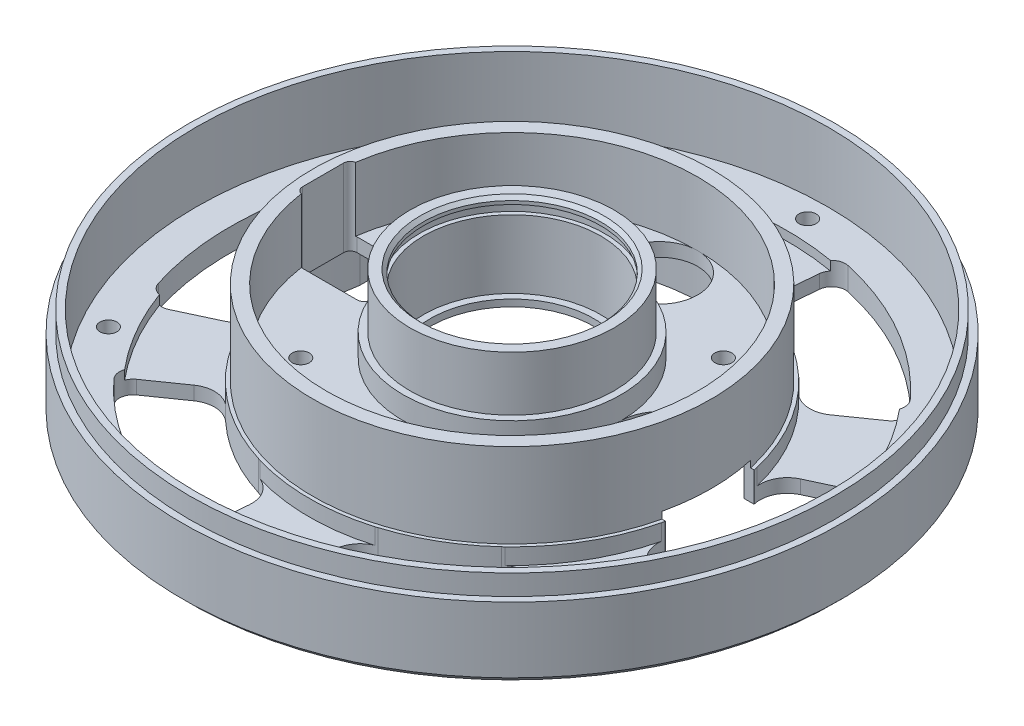
SolidWorks part; units mm, degrees
material "5052-H32"
ref_plane "Front Plane" through (0, 0, 0) normal (0, 0, 1) x (1, 0, 0)
ref_plane "Top Plane" through (0, 0, 0) normal (0, 1, 0) x (1, 0, 0)
ref_plane "Right Plane" through (0, 0, 0) normal (1, 0, 0) x (0, 0, -1)
ref_axis "Axis1" through (0, 0, 0) along (0, 1, 0)
sketch "Sketch1" plane through (0, 0, 0) normal (0, 0, 1) x (1, 0, 0)
  line L0 (0, 0) -> (0, -50000) construction
  line L1 (-13, 8.15) -> (-13, -4.15)
  line L2 (-13, -4.15) -> (-12, -4.15)
  line L4 (45.1, 8.15) -> (-45.1, 8.15) construction
  line L5 (-12.75, -4.15) -> (12.75, -4.15) construction
  line L7 (-13, 8.15) -> (-14.98, 8.15)
  line L8 (-14.98, 8.15) -> (-14.98, -3.15)
  line L9 (-14.98, -3.15) -> (-28.25, -3.15)
  line L10 (-12, -5.15) -> (-28.25, -5.15)
  line L12 (-28.25, -5.15) -> (-28.25, -3.15)
  line L13 (-29.25, 6) -> (-29.25, -6) construction
  line L16 (-12, -4.15) -> (-12, -5.15)
  dimension "D1" = 1
  dimension "D2" = 29.96
  dimension "D3" = 2
  dimension "D4" = 1
  dimension "D5" = 1
  dimension "D6" = 26
revolve "Revolve1" add sketch "Sketch1" angle 360 about L0
sketch "Sketch4" plane through (0, 0, 0) normal (0, 0, 1) x (1, 0, 0)
  line L1 (-29.75, -8.5) -> (-40.35, -8.5)
  line L2 (-46.35, -7.15) -> (-46.35, 3)
  line L3 (-46.35, 3) -> (-47.35, 3)
  line L4 (-47.35, 3) -> (-47.35, 0)
  line L5 (-47.35, 0) -> (-48.35, 0)
  line L6 (-48.35, 0) -> (-48.35, -9.6235)
  line L7 (-47.4735, -10.5) -> (-28.25, -10.5)
  line L8 (-28.25, -10.5) -> (-26.25, -5.15) construction
  line L9 (-29.75, -8.5) -> (-29.75, -6.1361)
  line L10 (-26.25, -5.15) -> (-26.25, -3.15)
  line L12 (-48.35, -9.6235) -> (-47.4735, -10.5)
  line L13 (-45.1, 8.15) -> (-45.1, -6.15) construction
  line L14 (-46.35, -7.15) -> (-40.35, -7.15)
  line L15 (-40.35, -7.15) -> (-40.35, -8.5)
  line L16 (-45.1, -6.15) -> (45.1, -6.15) construction
  line L18 (-44.85, -7.15) -> (-44.85, -10.5) construction
  line L20 (-41.85, -7.15) -> (-41.85, -10.5) construction
  line L21 (-26.25, -5.15) -> (-28.25, -5.15)
  line L22 (-29.75, -6.1361) -> (-29.23, -6.1361)
  line L23 (-28.25, -5.15) -> (-28.25, -10.5)
  line L24 (-29.23, -6.1361) -> (-29.23, -3.15)
  line L25 (-29.23, -3.15) -> (-26.25, -3.15)
  line L26 (28.25, -3.15) -> (-28.25, -3.15) construction
  line L27 (-39.5, -7.5) -> (39.5, -7.5) construction
  line L28 (0, 0) -> (0, 50000) construction
  line L29 (-30.25, -6) -> (-30.25, -7.5) construction
  line L33 (-28.25, -5.15) -> (28.25, -5.15) construction
  dimension "D1" = 2
  dimension "D2" = 3
  dimension "D3" = 1
  dimension "D4" = 2
  dimension "D5" = 0.5
  dimension "D6" = 1
  dimension "D7" = 1.25
  dimension "D8" = 135
  dimension "D9" = 3
  dimension "D10" = 1.5
  dimension "D11" = 1.5
  dimension "D12" = 2
  dimension "D13" = 1.5
  dimension "D14" = 58.46
revolve "Revolve2" add sketch "Sketch4" angle 360 about axis through (0, 0, 0) along (0, 1, 0)
sketch "Sketch6" plane through (0, 0, 0) normal (0, 0, 1) x (1, 0, 0)
  line L0 (-29.23, 6.233) -> (-27.23, 6.233)
  line L1 (-27.23, 6.233) -> (-27.23, -3.15)
  line L2 (-27.23, -3.15) -> (-29.23, -3.15)
  line L3 (-29.23, -3.15) -> (-29.23, 6.233)
  line L6 (29.23, -3.15) -> (-29.23, -3.15) construction
  dimension "D1" = 2
revolve "Revolve3" add sketch "Sketch6" angle 360 about axis through (0, 0, 0) along (0, 1, 0)
sketch "Sketch7" plane through (0, 0, 0) normal (0, 0, 1) x (1, 0, 0)
  line L0 (40.35, -8.5) -> (-40.35, -8.5) construction
  line L1 (-29.7176, -6.1376) -> (-29.23, -6.1376)
  line L2 (-29.73, -6.15) -> (-29.73, -8.5)
  line L3 (-29.73, -8.5) -> (-29.23, -8.5)
  line L4 (-29.23, -6.1376) -> (-29.23, -8.5)
  line L5 (-29.23, 6.233) -> (-29.23, -6.1361) construction
  line L6 (-29.7176, -6.1376) -> (-29.73, -6.15)
  line L7 (29.75, -8.5) -> (-29.75, -8.5) construction
  line L8 (-31.759, -6.15) -> (-25.7399, -6.15) construction
  dimension "D1" = 135
  dimension "D2" = 0.5
revolve "Revolve4" add sketch "Sketch7" angle 360 about axis through (0, 0, 0) along (0, 1, 0)
sketch "Sketch8" plane through (0, -5.15, 0) normal (0, -1, 0) x (1, 0, 0)
  circle A0 centre (-15.5, 15.5) radius 3.5
  circle A1 centre (15.5, 15.5) radius 3.5
  circle A2 centre (15.5, -15.5) radius 3.5
  circle A3 centre (-15.5, -15.5) radius 3.5
  dimension "D1" = 7
sketch "Sketch10" plane through (0, 0, 0) normal (0, 0, 1) x (1, 0, 0)
  line L0 (-15.25, 0.15) -> (15.25, 0.15) construction
  line L1 (-14.98, -3.15) -> (-15.98, -3.15)
  line L2 (-14.98, -3.15) -> (-14.98, 0.15)
  line L3 (-14.98, 0.15) -> (-15.98, 0.15)
  line L4 (-15.98, -3.15) -> (-15.98, 0.15)
  line L5 (-14.98, 8.15) -> (-14.98, -3.15) construction
  line L6 (14.98, -3.15) -> (-14.98, -3.15) construction
  dimension "D1" = 1
revolve "Revolve5" add sketch "Sketch10" angle 360 about axis through (0, 0, 0) along (0, 1, 0)
sketch "Sketch12" plane through (0, 0, 0) normal (0, 1, 0) x (1, 0, 0)
  circle A0 centre (21.605, 0) radius 5.625
  circle A1 centre (0, 0) radius 15.98 construction
  circle A2 centre (0, 0) radius 27.23 construction
extrude "Cut-Extrude2" cut sketch "Sketch12" against normal through all
pattern_circular "CirPattern3" count 4 over 360 about axis through (0, 0, 0) along (0, 1, 0) skipping 2, 3 of "Cut-Extrude2"
extrude "Boss-Extrude1" add sketch "Sketch8" along normal up to surface (3.85 mm away)
hole_wizard "M3x0.5 Tapped Hole1" positions "Sketch14" profile "Sketch15" tap size "M3x0.5" standard "ANSI Metric" end condition through all
sketch "Sketch14" plane through (0, -9, 0) normal (0, -1, 0) x (-1, 0, 0)
  point P0 (-15.5, 15.5)
  point P3 (15.5, 15.5)
  point P6 (15.5, -15.5)
  point P9 (-15.5, -15.5)
cosmetic thread "Hole Thread1" parameters "D2"=3
cosmetic thread "Hole Thread2" parameters "D2"=3
cosmetic thread "Hole Thread3" parameters "D2"=3
cosmetic thread "Hole Thread4" parameters "D2"=3
sketch "Sketch15" plane through (15.5, -9, -15.5) normal (1, 0, 0) x (0, 0, -1)
  line L0 (0, 0) -> (0, 17.15)
  line L1 (0, 17.15) -> (1.25, 17.15)
  line L2 (1.25, 17.15) -> (1.25, 0)
  line L5 (1.25, 0) -> (0, 0)
  line L11 (0, -6.35) -> (0, 107.95) construction
  dimension "Thru Tap Drill Dia." = 2.5
  dimension "Thru Tap Drill Depth" = 17.15
hole_wizard "M3x0.5 Tapped Hole3" positions "Sketch19" profile "Sketch20" tap size "M3x0.5" standard "ANSI Metric" end condition through all
sketch "Sketch19" plane through (0, -10.5, 0) normal (0, -1, 0) x (-1, 0, 0)
  line L0 (0, 0) -> (0, 43.35) construction
  line L3 (0, 0) -> (-50000, 0) construction
  circle A1 centre (0, 0) radius 43.35 construction
  circle A2 centre (0, 0) radius 40.35 construction
  point P0 (0, 43.35)
  dimension "D1" = 3
  dimension "D2" = 90
sketch "Sketch20" plane through (0, -10.5, -43.35) normal (1, 0, 0) x (0, 0, -1)
  line L0 (0, 0) -> (0, 18.65)
  line L1 (0, 18.65) -> (1.25, 18.65)
  line L2 (1.25, 18.65) -> (1.25, 0.5)
  line L3 (1.25, 0.5) -> (1.75, 0)
  line L5 (1.75, 0) -> (0, 0)
  line L6 (-1.25, 0.5) -> (-1.75, 0) construction
  line L11 (0, -6.35) -> (0, 107.95) construction
  dimension "Thru Tap Drill Dia." = 2.5
  dimension "Thru Tap Drill Depth" = 18.65
  dimension "Near C'Sink Dia." = 3.5
  dimension "Near C'Sink Angle" = 90
cosmetic thread "Hole Thread7" parameters "D2"=3
pattern_circular "CirPattern4" count 6 over 360 about axis through (0, 0, 0) along (0, 1, 0) of "M3x0.5 Tapped Hole3"
sketch "Sketch24" plane through (0, -10.5, 0) normal (0, -1, 0) x (1, 0, 0)
  line L9 (-25.6489, 5.5) -> (-44.2117, 5.5)
  line L10 (-25.6489, 5.5) -> (-25.6489, -5.5)
  line L11 (-25.6489, -5.5) -> (-44.2117, -5.5)
  line L12 (-46.2117, 3.5) -> (-46.2117, -3.5)
  arc A5 (-44.2117, -5.5) -> (-46.2117, -3.5) centre (-44.2117, -3.5) cw
  arc A6 (-44.2117, 5.5) -> (-46.2117, 3.5) centre (-44.2117, 3.5) ccw
  circle A7 centre (0, 0) radius 46.35 construction
  point P5 (-25.6489, 0)
  dimension "D2" = 2
  dimension "D1" = 11
extrude "Cut-Extrude6" [suppressed] cut sketch "Sketch24" against normal up to surface (1.5 mm away)
sketch "Sketch25" plane through (0, -10.5, 0) normal (0, -1, 0) x (1, 0, 0)
  line L5 (-25.6489, 5.5) -> (-44.2117, 5.5) construction
  line L9 (-34.6807, 5.5) -> (-44.2117, 5.5)
  line L10 (-34.6807, 5.5) -> (-34.6807, -5.5)
  line L11 (-34.6807, -5.5) -> (-44.2117, -5.5)
  line L12 (-46.2117, 3.5) -> (-46.2117, -3.5)
  line L13 (-25.6489, -5.5) -> (-44.2117, -5.5) construction
  line L14 (-46.2117, 3.5) -> (-46.2117, -3.5) construction
  arc A3 (-44.2117, -5.5) -> (-46.2117, -3.5) centre (-44.2117, -3.5) cw
  arc A4 (-44.2117, 5.5) -> (-46.2117, 3.5) centre (-44.2117, 3.5) ccw
  point P12 (-46.2117, -5.5)
  dimension "D1" = 2
extrude "Cut-Extrude7" [suppressed] cut sketch "Sketch25" against normal through all
sketch "Sketch26" plane through (0, 0, 0) normal (0, 1, 0) x (1, 0, 0)
  line L0 (0, 0) -> (-50000, 0) construction
  line L1 (31.1951, 11.1252) -> (36.6728, 13.6795)
  line L2 (31.1951, -11.1252) -> (36.6728, -13.6795)
  arc A0 (39.4249, 12.47) -> (39.4249, -12.47) centre (0, 0) cw
  arc A1 (28.9857, 6.6106) -> (28.9857, -6.6106) centre (0, 0) cw
  arc A2 (28.9857, -6.6106) -> (31.1951, -11.1252) centre (32.8856, -7.5) ccw
  arc A3 (28.9857, 6.6106) -> (31.1951, 11.1252) centre (32.8856, 7.5) cw
  circle A4 centre (0, 0) radius 46.35 construction
  arc A6 (39.4249, -12.47) -> (36.6728, -13.6795) centre (37.518, -11.8669) cw
  arc A7 (39.4249, 12.47) -> (36.6728, 13.6795) centre (37.518, 11.8669) ccw
  circle A8 centre (0, 0) radius 29.23 construction
  point P12 (28.108, -9.6857)
  point P15 (28.108, 9.6857)
  point P20 (38.6807, -14.6158)
  point P26 (38.6807, 14.6158)
  dimension "D1" = 4
  dimension "D2" = 0.5
  dimension "D4" = 2
  dimension "D6" = 5
  dimension "D3" = 50
  dimension "D5" = 15
extrude "Cut-Extrude8" cut sketch "Sketch26" against normal through all both and the other way through all
pattern_circular "CirPattern5" count 6 over 360 about axis through (0, 0, 0) along (0, 1, 0) of "Cut-Extrude8"
sketch "Sketch30" plane through (0, -10.5, 0) normal (0, -1, 0) x (1, 0, 0)
  line L1 (6.6135, 5) -> (34.3769, 5)
  line L2 (6.6135, 5) -> (6.6135, -5)
  line L3 (6.6135, -5) -> (34.3769, -5)
  line L4 (34.3769, 5) -> (34.3769, -5)
  point P4 (6.6135, 0)
  dimension "D1" = 10
extrude "Cut-Extrude13" [suppressed] cut sketch "Sketch30" against normal up to surface (5.35 mm away) up to face at (-15.5, -5.15, -19)
sketch "Sketch31" plane through (0, 0, 0) normal (0, 0, 1) x (1, 0, 0)
  line L0 (0, 0) -> (0, -50000) construction
  line L1 (13, 8.15) -> (-13, 8.15) construction
  line L2 (-5.4339, 7.15) -> (-13.6, 7.15)
  line L3 (-5.4339, 7.15) -> (-5.4339, 5.85)
  line L4 (-5.4339, 5.85) -> (-13.6, 5.85)
  line L5 (-13.6, 7.15) -> (-13.6, 5.85)
  dimension "D1" = 1.3
  dimension "D2" = 1
  dimension "D3" = 27.2
revolve "Cut-Revolve1" cut sketch "Sketch31" angle 360 about L0
chamfer "Chamfer1" distance 0.5 angle 45 1 edges at (0, 8.15, 13)
sketch "Sketch32" plane through (0, 0, 0) normal (0, 1, 0) x (1, 0, 0)
  line L1 (-18.73, 4) -> (-26.73, 4)
  line L2 (-17.73, 3) -> (-17.73, -3)
  line L3 (-18.73, -4) -> (-26.73, -4)
  line L4 (-27.73, 3) -> (-27.73, -3)
  arc A0 (-26.73, 4) -> (-27.73, 3) centre (-26.73, 3) ccw
  arc A1 (-17.73, -3) -> (-18.73, -4) centre (-18.73, -3) cw
  arc A2 (-26.73, -4) -> (-27.73, -3) centre (-26.73, -3) cw
  arc A3 (-18.73, 4) -> (-17.73, 3) centre (-18.73, 3) cw
  circle A4 centre (0, 0) radius 27.23 construction
  circle A5 centre (0, 0) radius 27.23 construction
  point P4 (-17.73, 0)
  point P16 (-27.23, 0)
  dimension "D2" = 1
  dimension "D3" = 0.5
  dimension "D1" = 8
  dimension "D4" = 10
extrude "Cut-Extrude14" cut sketch "Sketch32" against normal through all both and the other way through all
sketch "Sketch33" plane through (0, 0, 0) normal (0, 1, 0) x (1, 0, 0)
  line L1 (33.3439, -6.5) -> (25.7584, -6.5)
  line L2 (33.3439, -6.5) -> (33.3439, 6.5)
  line L3 (33.3439, 6.5) -> (25.7584, 6.5)
  line L4 (25.7584, -6.5) -> (25.7584, 6.5)
  line L5 (33.3439, -6.5) -> (25.7584, 6.5) construction
  line L6 (33.3439, 6.5) -> (25.7584, -6.5) construction
  point P0 (29.5512, 0)
  dimension "D1" = 13
extrude "Cut-Extrude15" cut sketch "Sketch33" along normal up to surface (-5.15 mm away) from offset 20 up to face at (-22.73, -5.15, 0) offset against normal yes
pattern_circular "CirPattern6" [suppressed] count 6 over 360 about axis through (0, 0, 0) along (0, 1, 0) of bodies 145
sketch "Sketch34" plane through (0, -5.15, 0) normal (0, -1, 0) x (1, 0, 0)
  line L0 (4.7, 19) -> (-2.3, 12) construction
  line L1 (-1.8, 19) -> (4.2, 19)
  line L2 (-2.3, 18.5) -> (-2.3, 12.5)
  line L3 (-1.8, 12) -> (4.2, 12)
  line L4 (4.7, 18.5) -> (4.7, 12.5)
  arc A0 (4.2, 19) -> (4.7, 18.5) centre (4.2, 18.5) cw
  arc A1 (-2.3, 12.5) -> (-1.8, 12) centre (-1.8, 12.5) ccw
  arc A2 (4.2, 12) -> (4.7, 12.5) centre (4.2, 12.5) ccw
  arc A3 (-1.8, 19) -> (-2.3, 18.5) centre (-1.8, 18.5) ccw
  point P4 (1.2, 15.5)
  dimension "D5" = 0.5
  dimension "D1" = 7
  dimension "D2" = 7
  dimension "D3" = 15.5
  dimension "D4" = 1.2
extrude "Boss-Extrude2" add sketch "Sketch34" along normal offset from surface (2.35 mm away) 1.5
sketch "Sketch35" plane through (0, 0, 0) normal (0, 1, 0) x (1, 0, 0)
  line L0 (-27.73, 3) -> (-27.73, -3) construction
  line L1 (-26.73, 7.5) -> (-21.2944, 7.5)
  line L2 (-27.73, 6.5) -> (-27.73, -6.5)
  line L3 (-26.73, -7.5) -> (-21.2944, -7.5)
  line L4 (-20.2944, 6.5) -> (-20.2944, -6.5)
  line L5 (-27.73, 7.5) -> (-20.2944, -7.5) construction
  line L6 (-27.73, -7.5) -> (-20.2944, 7.5) construction
  arc A0 (-21.2944, 7.5) -> (-20.2944, 6.5) centre (-21.2944, 6.5) cw
  arc A1 (-27.73, -6.5) -> (-26.73, -7.5) centre (-26.73, -6.5) ccw
  arc A2 (-26.73, 7.5) -> (-27.73, 6.5) centre (-26.73, 6.5) ccw
  arc A3 (-21.2944, -7.5) -> (-20.2944, -6.5) centre (-21.2944, -6.5) ccw
  point P0 (-24.0122, 0)
  dimension "D1" = 1
  dimension "D2" = 13
extrude "Cut-Extrude16" cut sketch "Sketch35" against normal through all from surface starting at face at (14.2425, -5.15, 0)
